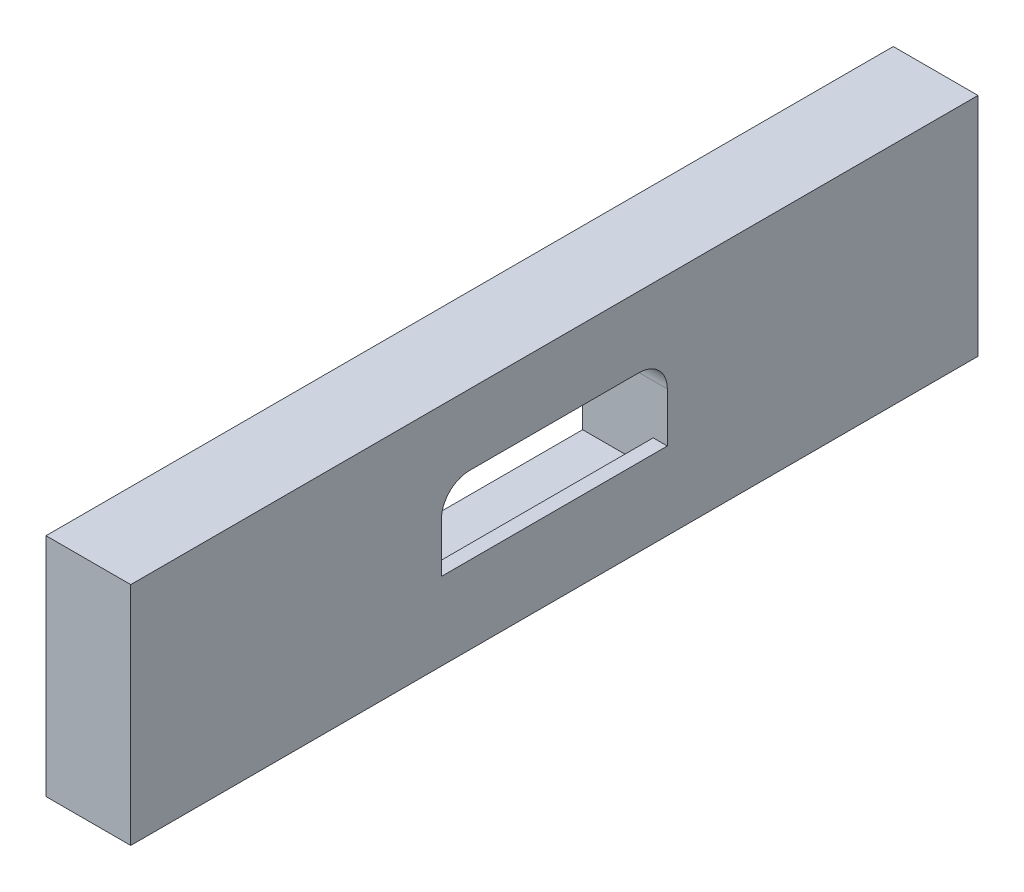
SolidWorks part; units mm, degrees
ref_plane "Front Plane" through (0, 0, 0) normal (0, 0, 1) x (1, 0, 0)
ref_plane "Top Plane" through (0, 0, 0) normal (0, 1, 0) x (1, 0, 0)
ref_plane "Right Plane" through (0, 0, 0) normal (1, 0, 0) x (0, 0, -1)
sketch "Sketch1" plane through (0, 0, 0) normal (1, 0, 0) x (0, 0, -1)
  line L1 (0, 0) -> (762, 0)
  line L2 (0, 0) -> (0, 203.2)
  line L3 (0, 203.2) -> (762, 203.2)
  line L4 (762, 0) -> (762, 203.2)
  dimension "D1" = 762
  dimension "D2" = 203.2
extrude "Boss-Extrude1" add sketch "Sketch1" along normal blind 76.2
sketch "Sketch2" plane through (0, 0, 0) normal (-1, 0, 0) x (0, 0, 1)
  line L1 (-482.6, 44.45) -> (-279.4, 44.45)
  line L2 (-482.6, 44.45) -> (-482.6, 139.7)
  line L3 (-482.6, 139.7) -> (-279.4, 139.7)
  line L4 (-279.4, 44.45) -> (-279.4, 139.7)
  line L6 (0, 0) -> (-762, 0) construction
  line L7 (-762, 0) -> (-762, 203.2) construction
  point P6 (-381, 139.7)
  dimension "D1" = 44.45
  dimension "D2" = 381
  dimension "D3" = 95.25
  dimension "D4" = 203.2
extrude "Cut-Extrude1" cut sketch "Sketch2" against normal blind 63.5
sketch "Sketch3" plane through (63.5, 0, 0) normal (-1, 0, 0) x (0, 0, 1)
  line L0 (-279.4, 44.45) -> (-279.4, 139.7) construction
  line L1 (-482.6, 139.7) -> (-279.4, 139.7)
  line L2 (-482.6, 139.7) -> (-482.6, 69.85)
  line L3 (-482.6, 69.85) -> (-279.4, 69.85)
  line L4 (-279.4, 139.7) -> (-279.4, 69.85)
  line L5 (-482.6, 44.45) -> (-279.4, 44.45) construction
  dimension "D1" = 25.4
extrude "Cut-Extrude2" cut sketch "Sketch3" against normal through all
fillet "Fillet1" radius 25.4 2 edges at (38.1, 139.7, -279.4) (38.1, 139.7, -482.6)
